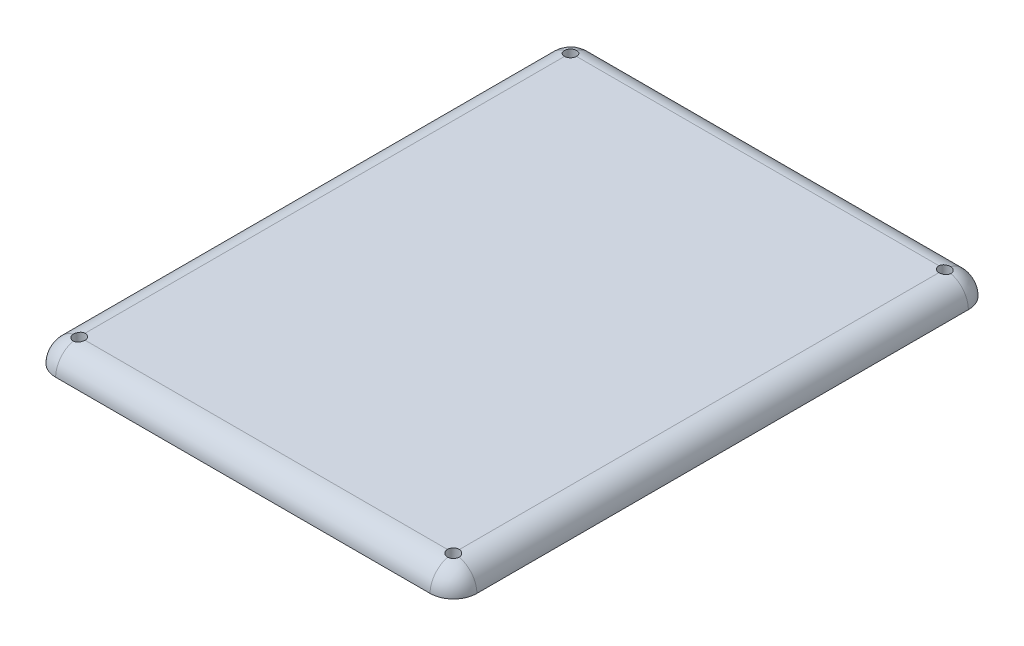
SolidWorks part; units mm, degrees
ref_plane "Front" through (0, 0, 0) normal (0, 0, 1) x (1, 0, 0)
ref_plane "Top" through (0, 0, 0) normal (0, 1, 0) x (1, 0, 0)
ref_plane "Right" through (0, 0, 0) normal (1, 0, 0) x (0, 0, -1)
sketch "Sketch1" plane through (0, 0, 0) normal (0, 1, 0) x (1, 0, 0)
  line L1 (-45, 57.5) -> (45, 57.5)
  line L2 (-45, 57.5) -> (-45, -57.5)
  line L3 (-45, -57.5) -> (45, -57.5)
  line L4 (45, 57.5) -> (45, -57.5)
  line L5 (-45, 57.5) -> (45, -57.5) construction
  line L6 (-45, -57.5) -> (45, 57.5) construction
  point P0 (0, 0)
extrude "Boss-Extrude1" add sketch "Sketch1" along normal blind 5
sketch "Sketch2" plane through (0, 0, 0) normal (0, -1, 0) x (1, 0, 0)
  line L0 (45, 57.5) -> (45, 52.5) construction
  line L1 (45, 57.5) -> (45, -57.5) construction
  line L2 (45, 52.5) -> (42.5, 52.5) construction
  line L3 (-45, 57.5) -> (-45, 52.5) construction
  line L4 (-45, -57.5) -> (-45, 57.5) construction
  line L5 (-45, 52.5) -> (-42.5, 52.5) construction
  line L6 (-45, -57.5) -> (-42.5, -57.5) construction
  line L7 (45, -57.5) -> (-45, -57.5) construction
  line L8 (-42.5, -57.5) -> (-42.5, -52.5) construction
  line L9 (45, -57.5) -> (42.5, -57.5) construction
  line L10 (42.5, -57.5) -> (42.5, -52.5) construction
sketch "Sketch3" plane through (0, 5, 0) normal (0, 1, 0) x (1, 0, 0)
  line L0 (-45, 57.5) -> (-45, 52.5) construction
  line L1 (-45, 57.5) -> (-45, -57.5) construction
  line L2 (-45, 52.5) -> (-42.5, 52.5) construction
  line L3 (-45, -52.5) -> (-42.5, -52.5) construction
  line L4 (45, -52.5) -> (42.5, -52.5) construction
  line L5 (45, 52.5) -> (42.5, 52.5) construction
  line L6 (45, -57.5) -> (45, 57.5) construction
  point P6 (0, 0)
fillet "Fillet4" radius 5 3 edges at (0, 5, 57.5) (45, 2.5, 57.5) (-45, 2.5, 57.5)
fillet "Fillet5" radius 5 3 edges at (-45, 5, -2.5) (-45, 3.5355, 56.0355) (-45, 2.5, -57.5)
fillet "Fillet6" radius 5 3 edges at (45, 5, -2.5) (45, 3.5355, 56.0355) (45, 2.5, -57.5)
fillet "Fillet7" radius 5 3 edges at (-43.5355, 3.5355, -57.5) (0, 5, -57.5) (43.5355, 3.5355, -57.5)
sketch "Sketch4" plane through (0, 0, 0) normal (0, -1, 0) x (1, 0, 0)
  line L0 (14.5, 35.9667) -> (40, 35.9667)
  line L5 (14.5, 35.9667) -> (14.5, 30.9667)
  line L6 (40, 35.9667) -> (40, 30.9667)
  line L7 (14.5, 30.9667) -> (40, 30.9667)
extrude "Boss-Extrude2" add sketch "Sketch4" along normal blind 5
fillet "Fillet12" radius 2.5 1 edges at (27.25, -5, 35.9667)
fillet "Fillet13" radius 2.5 3 edges at (40, -5, 32.2167) (27.25, -5, 30.9667) (14.5, -5, 32.2167)
sketch "Sketch7" plane through (0, 0, 0) normal (0, -1, 0) x (1, 0, 0)
  line L1 (-45, -52.5) -> (-38.3526, -52.5) construction
  line L2 (-40, -57.5) -> (-40, -52.5) construction
  line L3 (40, -57.5) -> (40, -52.5) construction
  line L4 (40, 57.5) -> (40, 52.5) construction
  line L5 (-45, 52.5) -> (-40, 52.5) construction
  circle A0 centre (-40, -52.5) radius 1.27
  circle A2 centre (40.004, -52.4698) radius 1.27
  circle A3 centre (39.9617, 52.4945) radius 1.27
  circle A4 centre (-39.9807, 52.4822) radius 1.27
  point P22 (0, 0)
extrude "Cut-Extrude2" cut sketch "Sketch7" against normal through all contours A4 | A3 | A2 | A0
